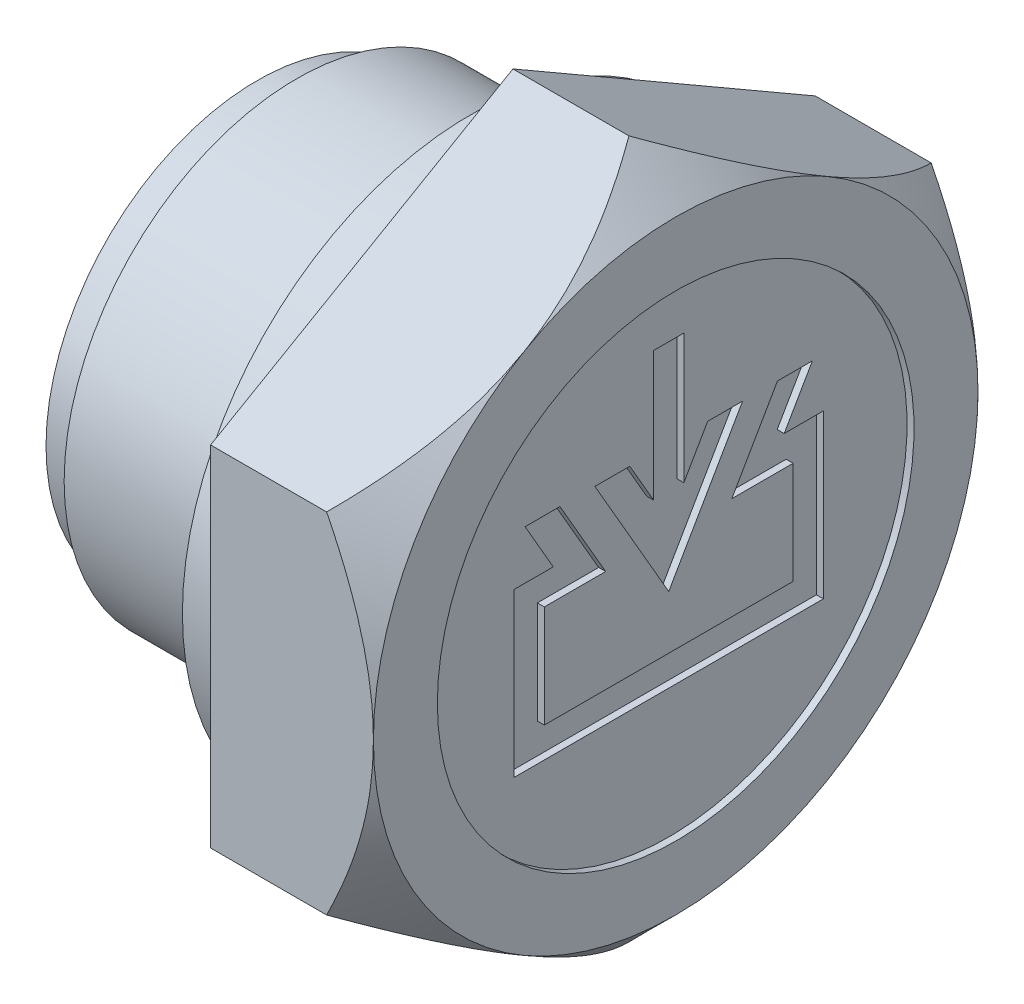
SolidWorks part; units mm, degrees
ref_plane "Piano frontale" through (0, 0, 0) normal (0, 0, 1) x (1, 0, 0)
ref_plane "Piano superiore" through (0, 0, 0) normal (0, 1, 0) x (1, 0, 0)
ref_plane "Piano destro" through (0, 0, 0) normal (1, 0, 0) x (0, 0, -1)
ref_plane "Piano1" through (0, 0, 0) normal (0, 0, 1) x (1, 0, 0)
sketch "Schizzo1" plane through (0, 0, 0) normal (0, 0, 1) x (1, 0, 0)
  line L0 (14.2, 0) -> (14.2, 5.6879)
  line L1 (13.7174, 6.1876) -> (0, 6.6667)
  line L2 (0, 6.6667) -> (0, 9.0798)
  line L3 (0, 9.0798) -> (1.7, 9.0798)
  line L4 (1.7, 9.0798) -> (1.7, 10)
  line L5 (1.7, 10) -> (9.1667, 10)
  line L6 (9.1667, 10) -> (9.1667, 12.381)
  line L7 (9.1667, 12.381) -> (11, 12.381)
  line L8 (11, 12.381) -> (11, 20)
  line L9 (11, 20) -> (18, 13)
  line L10 (18, 13) -> (18, 10.25)
  line L11 (18, 10.25) -> (17.7, 10.25)
  line L12 (17.7, 10.25) -> (17.7, 0)
  line L13 (17.7, 0) -> (14.2, 0)
  line L14 (18, 0) -> (0, 0) construction
  arc A0 (14.2, 5.6879) -> (13.7174, 6.1876) centre (13.7, 5.6879) ccw
revolve "Rivoluzione1" add sketch "Schizzo1" angle 360 about L14 reverse direction yes
cosmetic thread "Filettatura cosmetica1" parameters "D1"=5, "D2"=18.16
ref_plane "Piano2" through (17.7, 0, 0) normal (1, 0, 0) x (0, 0, -1)
sketch "Schizzo2" plane through (17.7, 0, 0) normal (1, 0, 0) x (0, 0, -1)
  line L0 (-6.65, -4.7) -> (6.65, -4.7)
  line L1 (6.65, -4.7) -> (6.65, 2.3)
  line L2 (6.65, 2.3) -> (4.9652, 2.3)
  line L3 (4.9652, 2.3) -> (6.1776, 4.4)
  line L4 (6.1776, 4.4) -> (4.6765, 4.4)
  line L5 (4.6765, 4.4) -> (2.7135, 1)
  line L6 (2.7135, 1) -> (5.35, 1)
  line L7 (5.35, 1) -> (5.35, -3.4)
  line L8 (5.35, -3.4) -> (-5.35, -3.4)
  line L9 (-5.35, -3.4) -> (-5.35, 1)
  line L10 (-5.35, 1) -> (-2.7135, 1)
  line L11 (-2.7135, 1) -> (-4.6765, 4.4)
  line L12 (-4.6765, 4.4) -> (-6.1776, 4.4)
  line L13 (-6.1776, 4.4) -> (-4.9652, 2.3)
  line L14 (-4.9652, 2.3) -> (-6.65, 2.3)
  line L15 (-6.65, 2.3) -> (-6.65, -4.7)
extrude "Taglio-Estrusione1" cut sketch "Schizzo2" against normal blind 0.3 and the other way blind 0.3
ref_plane "Piano3" through (17.7, 0, 0) normal (1, 0, 0) x (0, 0, -1)
sketch "Schizzo3" plane through (17.7, 0, 0) normal (1, 0, 0) x (0, 0, -1)
  line L0 (-3.1754, 4.4) -> (0, -1.1)
  line L1 (0, -1.1) -> (3.1754, 4.4)
  line L2 (3.1754, 4.4) -> (1.6743, 4.4)
  line L3 (1.6743, 4.4) -> (0.65, 2.6258)
  line L4 (0.65, 2.6258) -> (0.65, 8.2)
  line L5 (0.65, 8.2) -> (-0.65, 8.2)
  line L6 (-0.65, 8.2) -> (-0.65, 2.6258)
  line L7 (-0.65, 2.6258) -> (-1.6743, 4.4)
  line L8 (-1.6743, 4.4) -> (-3.1754, 4.4)
extrude "Taglio-Estrusione2" cut sketch "Schizzo3" against normal blind 0.3 and the other way blind 0.3
ref_plane "Piano4" through (17.7, 0, 0) normal (1, 0, 0) x (0, 0, -1)
sketch "Schizzo4" plane through (17.7, 0, 0) normal (1, 0, 0) x (0, 0, -1)
  line L0 (-26, -15.0111) -> (0, -30.0222)
  line L1 (0, -30.0222) -> (26, -15.0111)
  line L2 (26, -15.0111) -> (26, 15.0111)
  line L3 (26, 15.0111) -> (0, 30.0222)
  line L4 (0, 30.0222) -> (-26, 15.0111)
  line L5 (-26, 15.0111) -> (-26, -15.0111)
  line L6 (-13, -7.5056) -> (0, -15.0111)
  line L7 (0, -15.0111) -> (13, -7.5056)
  line L8 (13, -7.5056) -> (13, 7.5056)
  line L9 (13, 7.5056) -> (0, 15.0111)
  line L10 (0, 15.0111) -> (-13, 7.5056)
  line L11 (-13, 7.5056) -> (-13, -7.5056)
extrude "Taglio-Estrusione3" cut sketch "Schizzo4" against normal blind 10.701 and the other way blind 10.701
